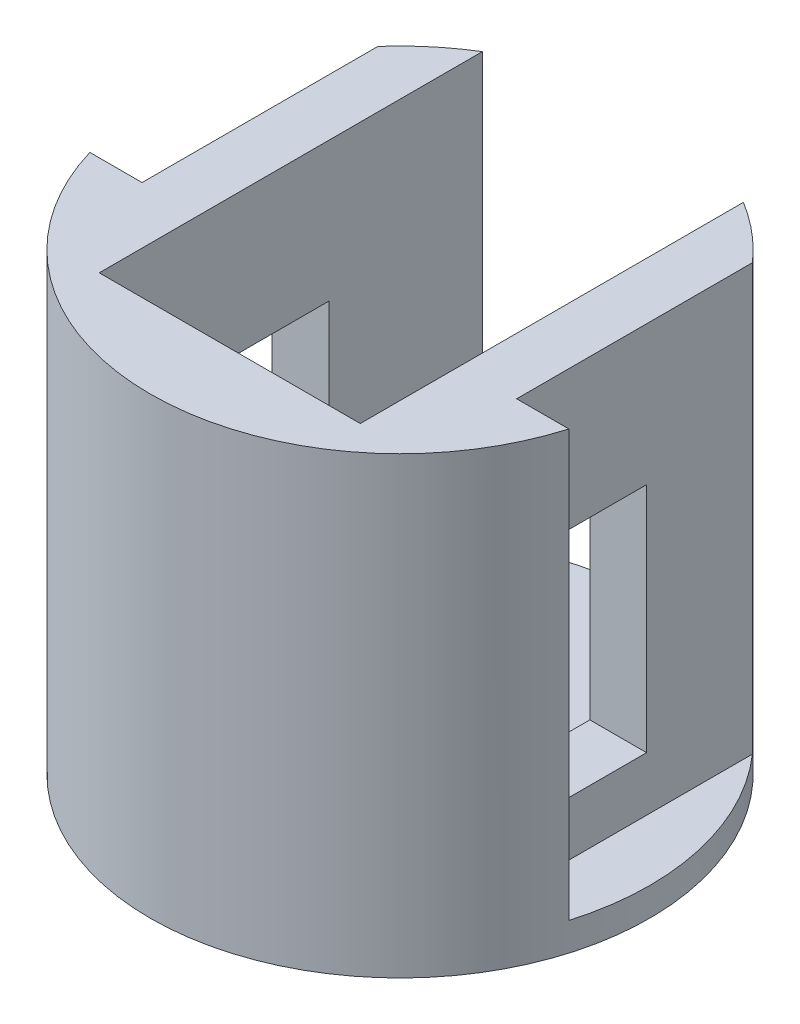
SolidWorks part; units mm, degrees
ref_plane "前视基准面" through (0, 0, 0) normal (0, 0, 1) x (1, 0, 0)
ref_plane "上视基准面" through (0, 0, 0) normal (0, 1, 0) x (1, 0, 0)
ref_plane "右视基准面" through (0, 0, 0) normal (1, 0, 0) x (0, 0, -1)
sketch "草图1" plane through (0, 0, 0) normal (0, 1, 0) x (1, 0, 0)
  circle A0 centre (0, 0) radius 44
  dimension "D1" = 88
extrude "凸台-拉伸1" add sketch "草图1" along normal blind 80
sketch "草图2" plane through (0, 0, 0) normal (0, 1, 0) x (1, 0, 0)
  line L0 (33, 29.1033) -> (33, -12.45)
  line L1 (33, -12.45) -> (42.2019, -12.45)
  line L2 (36.6, -9.45) -> (56.9, -9.45) construction
  line L3 (0, 44) -> (0, -30)
  line L4 (0, -30) -> (23, -30)
  line L5 (23, -30) -> (23, 44)
  line L6 (23, 44) -> (0, 44)
  circle A1 centre (0, 0) radius 44 construction
  arc A2 (42.2019, -12.45) -> (33, 29.1033) centre (0, 0) ccw
  dimension "D1" = 33
  dimension "D2" = 3
  dimension "D3" = 10
  dimension "D4" = 30
extrude "切除-拉伸5" cut sketch "草图2" along normal through all from offset 5
mirror "镜向1" about plane through (0, 0, 0) normal (1, 0, 0) of "切除-拉伸5"
sketch "草图3" plane through (33, 0, 0) normal (1, 0, 0) x (0, 0, -1)
  line L0 (-9.45, 54.95) -> (9.45, 54.95) construction
  line L1 (-10.45, 55.45) -> (10.45, 55.45)
  line L2 (-10.45, 55.45) -> (-10.45, 14.55)
  line L3 (-10.45, 14.55) -> (10.45, 14.55)
  line L4 (10.45, 55.45) -> (10.45, 14.55)
  line L5 (-9.95, 54.45) -> (-9.95, 15.55) construction
  line L6 (9.95, 54.45) -> (9.95, 15.55) construction
  line L7 (-9.45, 15.05) -> (9.45, 15.05) construction
  dimension "D1" = 0.5
  dimension "D2" = 0.5
  dimension "D3" = 0.5
  dimension "D4" = 0.5
extrude "切除-拉伸6" cut sketch "草图3" against normal through all
